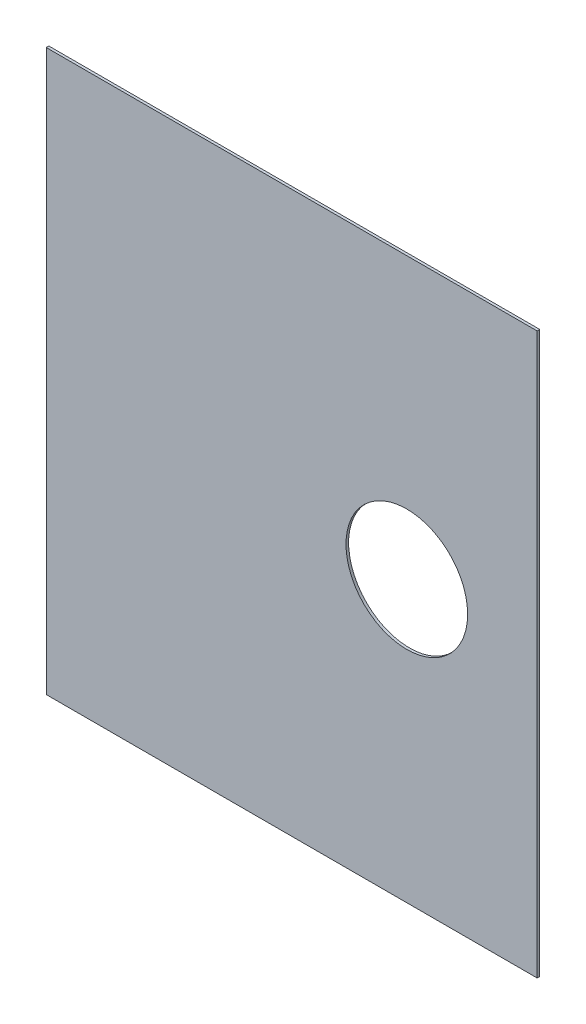
SolidWorks part; units mm, degrees
ref_plane "Přední rovina" through (0, 0, 0) normal (0, 0, 1) x (1, 0, 0)
ref_plane "Horní rovina" through (0, 0, 0) normal (0, 1, 0) x (1, 0, 0)
ref_plane "Pravá rovina" through (0, 0, 0) normal (1, 0, 0) x (0, 0, -1)
sketch "Skica1" plane through (0, 0, 0) normal (0, 0, 1) x (1, 0, 0)
  line L1 (-282.5, 322.5) -> (282.5, 322.5)
  line L2 (-282.5, 322.5) -> (-282.5, -322.5)
  line L3 (-282.5, -322.5) -> (282.5, -322.5)
  line L4 (282.5, 322.5) -> (282.5, -322.5)
  line L5 (-282.5, 322.5) -> (282.5, -322.5) construction
  line L6 (-282.5, -322.5) -> (282.5, 322.5) construction
  circle A0 centre (132.5, 0) radius 70
  point P0 (0, 0)
  dimension "D3" = 140
  dimension "D1" = 565
  dimension "D2" = 645
  dimension "D4" = 322.5
  dimension "D5" = 150
extrude "Přidat vysunutím1" add sketch "Skica1" along normal blind 3
